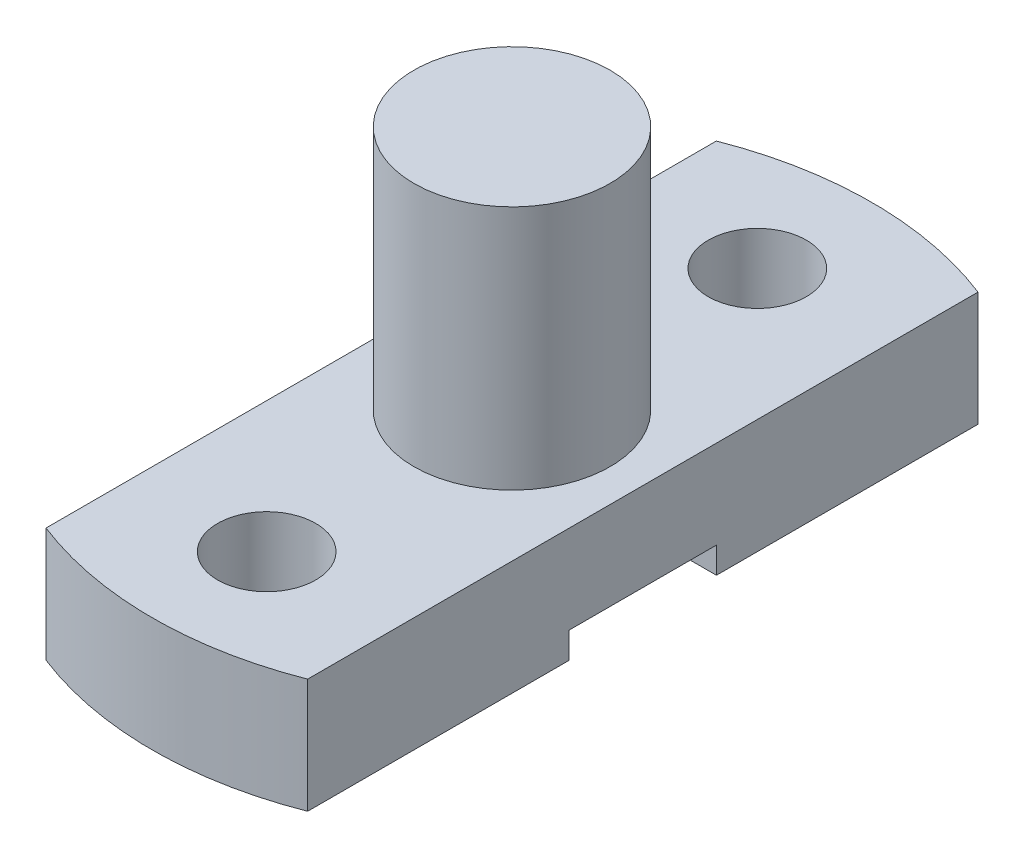
SolidWorks part; units mm, degrees
ref_plane "Front Plane" through (0, 0, 0) normal (0, 0, 1) x (1, 0, 0)
ref_plane "Top Plane" through (0, 0, 0) normal (0, 1, 0) x (1, 0, 0)
ref_plane "Right Plane" through (0, 0, 0) normal (1, 0, 0) x (0, 0, -1)
sketch "Sketch1" plane through (0, 0, 0) normal (0, 1, 0) x (1, 0, 0)
  line L0 (0, 118.5384) -> (0, -94.8347) construction
  line L1 (-151.2057, 0) -> (179.7075, 0) construction
  line L2 (-40, 102.4695) -> (-40, -102.4695)
  line L3 (40, 102.4695) -> (40, -102.4695)
  circle A0 centre (0, 75) radius 15
  circle A1 centre (0, -75) radius 15
  arc A2 (40, 102.4695) -> (-40, 102.4695) centre (0, 0) ccw
  arc A3 (-40, -102.4695) -> (40, -102.4695) centre (0, 0) ccw
  circle A4 centre (0, 0) radius 30
  circle A5 centre (0, 0) radius 22.5
  dimension "D2" = 30
  dimension "D3" = 220
  dimension "D7" = 60
  dimension "D8" = 45
  dimension "D1" = 150
  dimension "D4" = 80
  dimension "D5" = 40
  dimension "D6" = 75
extrude "Boss-Extrude1" add sketch "Sketch1" along normal blind 110 contours A4 A5 | A5 region at (-29.1515, 0, 0) region at (0, 0, 0)
extrude "Boss-Extrude2" add sketch "Sketch1<3>" along normal blind 35 contours L2 A3 L3 A2 A4 A0 A1 region at (0, 0, -107.6591)
sketch "Sketch1<3>" plane through (0, 0, 0) normal (0, 1, 0) x (1, 0, 0) same geometry as "Sketch1"
sketch "Sketch2" plane through (40, 0, 0) normal (1, 0, 0) x (0, 0, -1)
  line L0 (-22.5, 0) -> (-22.5, 8)
  line L1 (102.4695, 0) -> (-102.4695, 0) construction
  line L2 (-22.5, 8) -> (22.5, 8)
  line L3 (22.5, 8) -> (22.5, 0)
  line L4 (-22.5, 0) -> (22.5, 0)
  dimension "D1" = 45
  dimension "D2" = 22.5
  dimension "D3" = 8
extrude "Cut-Extrude2" cut sketch "Sketch2" against normal through all
